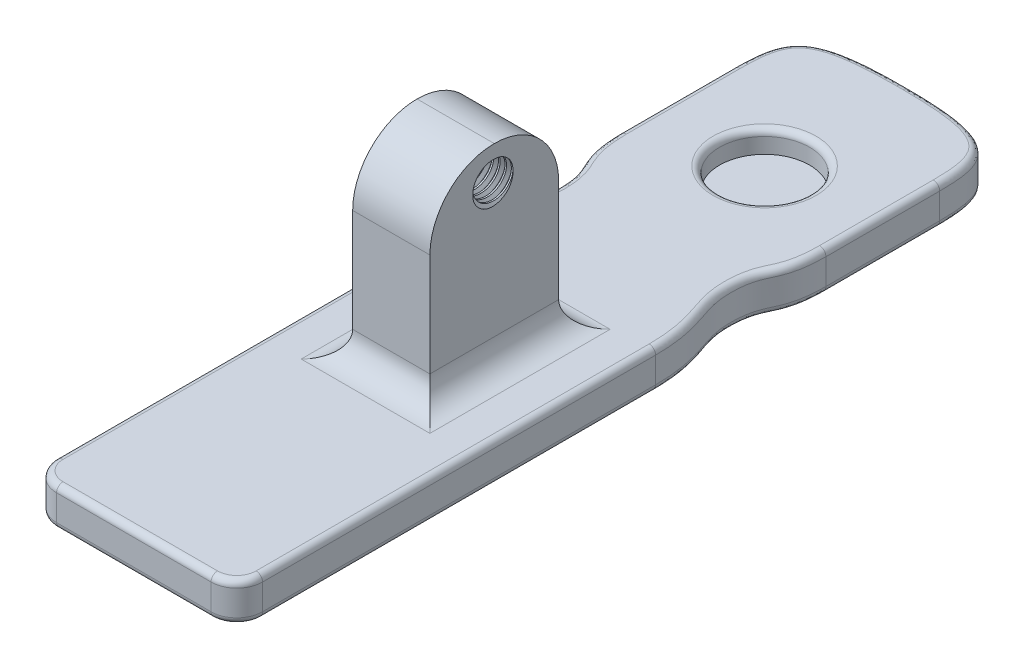
SolidWorks part; units mm, degrees
ref_plane "Front Plane" through (0, 0, 0) normal (0, 0, 1) x (1, 0, 0)
ref_plane "Top Plane" through (0, 0, 0) normal (0, 1, 0) x (1, 0, 0)
ref_plane "Right Plane" through (0, 0, 0) normal (1, 0, 0) x (0, 0, -1)
sketch "Sketch2" plane through (0, 0, 0) normal (0, 1, 0) x (1, 0, 0)
  line L1 (-3.1239, 28.5398) -> (12.8761, 28.5398)
  line L2 (-3.1239, 28.5398) -> (-3.1239, -31.4602)
  line L3 (-3.1239, -31.4602) -> (12.8761, -31.4602)
  line L4 (12.8761, 28.5398) -> (12.8761, -31.4602)
  dimension "D1" = 60
  dimension "D2" = 16
extrude "Boss-Extrude1" add sketch "Sketch2" along normal blind 3
sketch "Sketch3" plane through (0, 3, 0) normal (0, 1, 0) x (1, 0, 0)
  line L0 (4.8761, 28.5398) -> (4.8761, -31.4602) construction
  line L5 (12.8761, 28.5398) -> (-3.1239, 28.5398) construction
  line L6 (-3.1239, -31.4602) -> (12.8761, -31.4602) construction
  line L11 (1.8761, -1.4602) -> (7.8761, -1.4602)
  line L12 (1.8761, -1.4602) -> (1.8761, -11.4602)
  line L13 (1.8761, -11.4602) -> (7.8761, -11.4602)
  line L14 (7.8761, -1.4602) -> (7.8761, -11.4602)
  line L15 (1.8761, -1.4602) -> (7.8761, -11.4602) construction
  line L16 (1.8761, -11.4602) -> (7.8761, -1.4602) construction
  circle A0 centre (4.8761, 17.5398) radius 3.5
  point P11 (4.8761, -6.4602)
  point P12 (4.8761, -6.4602)
  dimension "D4" = 7
  dimension "D1" = 10
  dimension "D2" = 6
  dimension "D3" = 20
  dimension "D5" = 11
extrude "Boss-Extrude2" add sketch "Sketch3" along normal blind 15 contours L12 L13 L14 L11
extrude "Cut-Extrude1" cut sketch "Sketch3<3>" against normal blind 1.7 contours A0
sketch "Sketch3<3>" plane through (0, 3, 0) normal (0, 1, 0) x (1, 0, 0) same geometry as "Sketch3"
fillet "Fillet2" radius 2 4 edges at (4.8761, 3, 1.4602) (1.8761, 3, 6.4602) (4.8761, 3, 11.4602) (7.8761, 3, 6.4602)
sketch "Sketch4" plane through (1.8761, 0, 0) normal (-1, 0, 0) x (0, 0, 1)
  line L0 (6.4602, 18) -> (6.4602, 3) construction
  line L1 (1.4602, 18) -> (11.4602, 18) construction
  line L2 (13.4602, 3) -> (-0.5398, 3) construction
  circle A0 centre (6.4602, 15.5) radius 1.45
  dimension "D2" = 2.9
  dimension "D1" = 2.5
extrude "Cut-Extrude2" cut sketch "Sketch4" against normal through all contours A0
fillet "Fillet4" radius 5 2 edges at (4.8761, 18, 1.4602) (4.8761, 18, 11.4602)
thread "Thread1" pitch 0.5 method cut profile "Thread Profile1" start angle 0, offset 0, length 0, pitch 0.5, diameter 2.9
ref_plane "Plane1" through (1.8761, 15.5, 5.0102) normal (0, -1, 0) x (0, 0, -1)
sketch "Thread Profile1" plane through (1.8761, 15.5, 5.0102) normal (0, -1, 0) x (0, 0, -1)
  line L0 (0, 0) -> (0, 0.5) construction
  line L1 (0, 0) -> (0.2706, 0.1562)
  line L2 (0.2706, 0.1562) -> (0.2706, 0.2187)
  line L3 (0.2706, 0.2187) -> (0, 0.375)
  line L4 (0.2706, 0.1875) -> (0, 0.1875) construction
  line L11 (0, 0) -> (0, 0.375)
  point P2 (0, 0)
  dimension "Pitch" = 0.5
  dimension "Profile_Angle" = 60
  dimension "Profile_Land" = 0.0625
  dimension "Profile_Height" = 0.2706
sketch "Sketch7" plane through (0, 0, 0) normal (0, -1, 0) x (1, 0, 0)
  line L0 (4.8761, -28.5398) -> (4.8761, 31.4602) construction
  line L1 (12.8761, -28.5398) -> (-3.1239, -28.5398) construction
  line L2 (-3.1239, 31.4602) -> (12.8761, 31.4602) construction
  line L3 (-3.1239, -28.5398) -> (-3.1239, 31.4602) construction
  line L4 (-3.1239, -23.1393) -> (-3.1239, -28.5398)
  line L5 (-3.1239, -28.5398) -> (12.8761, -28.5398)
  line L6 (-3.1239, -14.3051) -> (-3.1239, -1.0727)
  line L7 (12.8761, -23.1393) -> (12.8761, -28.5398)
  line L8 (12.8761, -14.3051) -> (12.8761, -1.0727)
  spline S0 degree 3 poles (4.8761, -28.5398) (-2.2995, -28.5551) (-3.1053, -27.2751) (-3.1239, -23.1393) knots 0 0 0 0 1 1 1 1
  spline S1 degree 3 poles (-3.1239, -1.0727) (-3.1149, -4.5986) (-1.7974, -5.8753) (-1.8731, -11.1051) (-3.0891, -10.8792) (-3.1239, -14.3051) knots 0 0 0 0 0.399716 0.499716 1 1 1 1
  spline S2 degree 3 poles (12.8761, -1.0727) (12.8671, -4.5986) (11.5496, -5.8753) (11.6253, -11.1051) (12.8413, -10.8792) (12.8761, -14.3051) knots 0 0 0 0 0.399716 0.499716 1 1 1 1
  spline S3 degree 3 poles (4.8761, -28.5398) (12.0517, -28.5551) (12.8575, -27.2751) (12.8761, -23.1393) knots 0 0 0 0 1 1 1 1
  line M6 (-3.1239, 31.4602) -> (-3.1239, -28.5398)
  line M7 (-3.1239, -28.5398) -> (12.8761, -28.5398)
  line M8 (12.8761, -28.5398) -> (12.8761, 31.4602)
extrude "Cut-Extrude3" cut sketch "Sketch7" against normal up to surface (3 mm away) contours S0 M7 M6 | S1 M6 | S2 M8 | S3 L5 M8 region at (-1.7825, 0, -27.6731) region at (12.3936, 0, -7.9722) region at (11.5347, 0, -27.6731) region at (-2.6414, 0, -7.9716) up to face at (4.8761, 3, 6.4602)
fillet "Fillet1" radius 2 2 edges at (-3.1239, 1.5, 31.4602) (12.8761, 1.5, 31.4602)
fillet "Fillet3" radius 0.5 25 edges at (12.2903, 0, 30.8744) (12.8761, 0, 14.1937) (4.8761, 0, -28.5398) (-3.1239, 0, 14.1937) (-2.5381, 0, 30.8744) (4.8761, 0, 31.4602) (4.8761, 3, -28.5398) (12.8761, 3, 14.1937) (12.2903, 3, 30.8744) (4.8761, 3, 31.4602) (-2.5381, 3, 30.8744) (-3.1239, 3, 14.1937) (4.8761, 3, -14.0398) (12.8761, 0, -18.7222) (-3.1239, 0, -18.7222) (-3.1239, 3, -18.7222) (12.8761, 3, -18.7222)
